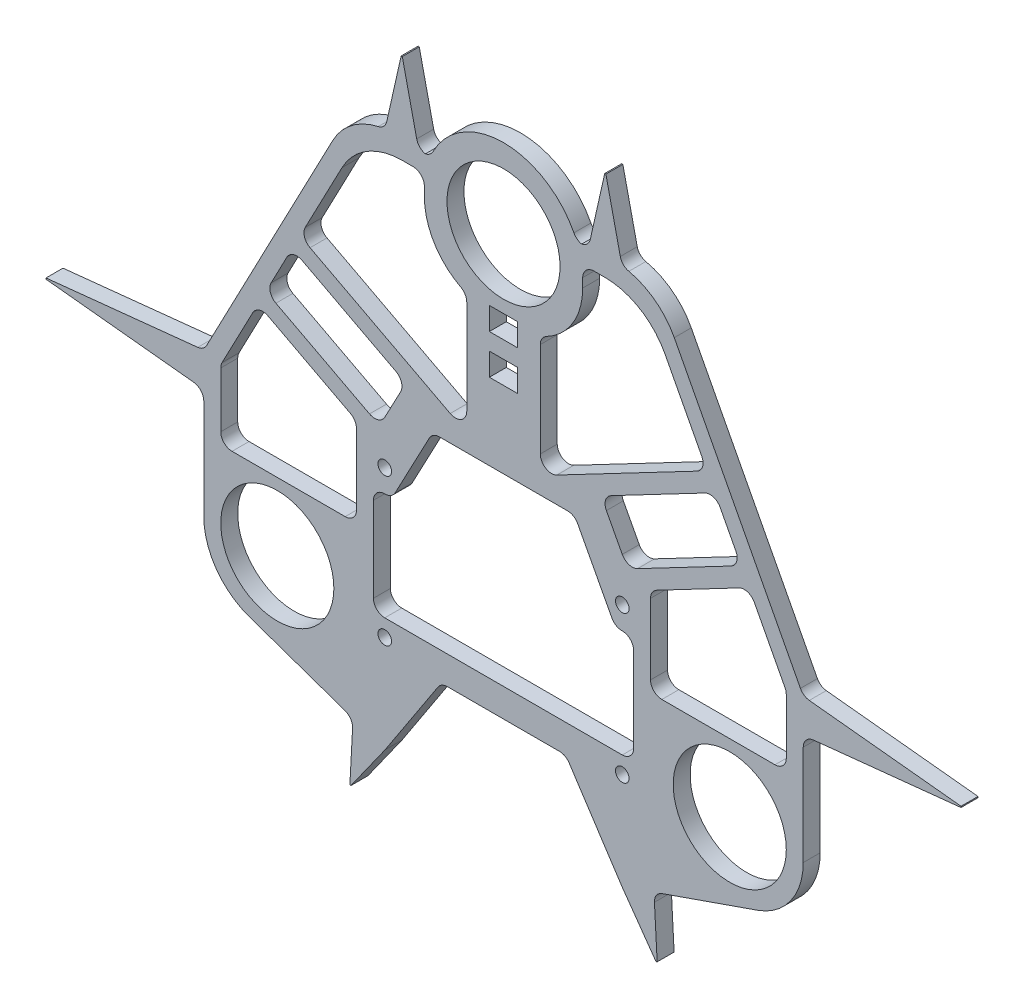
SolidWorks part; units mm, degrees
ref_plane "Plan de face" through (0, 0, 0) normal (0, 0, 1) x (1, 0, 0)
ref_plane "Plan de dessus" through (0, 0, 0) normal (0, 1, 0) x (1, 0, 0)
ref_plane "Plan de droite" through (0, 0, 0) normal (1, 0, 0) x (0, 0, -1)
sketch "Esquisse1" plane through (0, 0, 0) normal (0, 0, 1) x (1, 0, 0)
  line L0 (-40, 0) -> (40, 0) construction
  line L1 (40, 0) -> (0, 69.282) construction
  line L2 (0, 69.282) -> (-40, 0) construction
  line L3 (0, 0) -> (0, 69.282) construction
  line L12 (53, -24) -> (53, 25) construction
  line L13 (-53, 74.6) -> (53, 74.6) construction
  line L14 (-53, 74.6) -> (-53, -24) construction
  line L15 (-53, -24) -> (53, -24) construction
  line L16 (53, 74.6) -> (53, -24) construction
  line L17 (53, 25) -> (27, 74.6) construction
  line L18 (27, 74.6) -> (-27, 74.6) construction
  line L19 (-27, 74.6) -> (-53, 25) construction
  line L20 (-53, 25) -> (-53, -24) construction
  line L21 (40, 25) -> (-40, 25) construction
  line L22 (-40, 4) -> (40, 4) construction
  line L23 (-40, 4) -> (-40, -4) construction
  line L24 (-40, -4) -> (40, -4) construction
  line L25 (40, 4) -> (40, -4) construction
  line L26 (-34, 29) -> (34, 29) construction
  line L27 (-34, 29) -> (-34, 21) construction
  line L28 (-34, 21) -> (34, 21) construction
  line L29 (34, 29) -> (34, 21) construction
  line L30 (-4, 69.282) -> (4, 69.282) construction
  line L31 (-4, 69.282) -> (-4, -4) construction
  line L32 (-4, -4) -> (4, -4) construction
  line L33 (4, 69.282) -> (4, -4) construction
  line L34 (34, 39) -> (34, 11) construction
  line L81 (-27, 74.6) -> (27, 74.6) construction
  line L83 (53, 25) -> (53, -24) construction
  line L84 (53, -24) -> (-53, -24) construction
  line L85 (-53, -24) -> (-53, 25) construction
  line L103 (-53, -9) -> (-10, -24) construction
  line L104 (53, 25) -> (80.9, 22.1)
  line L105 (80.9, 22.1) -> (80.9, 21.9)
  line L106 (80.9, 21.9) -> (53, 19)
  line L107 (53, 19) -> (53, -9)
  line L108 (53, -9) -> (10, -24) construction
  line L109 (10, -24) -> (-10, -24) construction
  line L110 (-53, 19) -> (-53, -9)
  line L111 (-80.9, 21.9) -> (-53, 19)
  line L112 (-53, 25) -> (-80.9, 22.1)
  line L113 (-80.9, 22.1) -> (-80.9, 21.9)
  line L114 (53, 22) -> (80.9, 22) construction
  line L116 (21, 74.6) -> (18.1, 87.5)
  line L117 (18.1, 87.5) -> (17.9, 87.5)
  line L118 (17.9, 87.5) -> (15, 74.6)
  line L119 (15, 74.6) -> (-15, 74.6) construction
  line L120 (15, 74.6) -> (21, 74.6) construction
  line L121 (18, 74.6) -> (18, 87.5) construction
  line L122 (-17.9, 87.5) -> (-15, 74.6)
  line L123 (-18.1, 87.5) -> (-17.9, 87.5)
  line L124 (-21, 74.6) -> (-18.1, 87.5)
  line L126 (-15, 74.6) -> (-12.9506, 74.6)
  line L127 (15, 74.6) -> (12.9506, 74.6)
  line L128 (-53, -9) -> (-20, -20.5116) construction
  line L131 (20, -20.5116) -> (53, -9) construction
  line L132 (-20, -20.5116) -> (20, -20.5116) construction
  line L133 (53, -9) -> (26.6094, -18.206)
  line L134 (26.6094, -18.206) -> (27.1649, -28.6032)
  line L135 (27.1649, -28.6032) -> (26.9761, -28.6691)
  line L136 (26.9761, -28.6691) -> (20.9442, -20.1823)
  line L138 (-53, -9) -> (-26.6094, -18.206)
  line L139 (-26.6094, -18.206) -> (-27.1649, -28.6032)
  line L140 (-27.1649, -28.6032) -> (-26.9761, -28.6691)
  line L141 (-26.9761, -28.6691) -> (-20.9442, -20.1823)
  line L143 (20.9442, -20.1823) -> (26.6094, -18.206) construction
  line L144 (23.7768, -19.1941) -> (27.0705, -28.6361) construction
  line L145 (-40, 0) -> (20, 34.641) construction
  line L146 (40, 0) -> (-20, 34.641) construction
  line L147 (-2.5, 53.094) -> (2.5, 53.094)
  line L148 (-2.5, 57.094) -> (2.5, 57.094)
  line L149 (-2.5, 57.094) -> (-2.5, 53.094)
  line L151 (2.5, 57.094) -> (2.5, 53.094)
  line L196 (-47, 23) -> (-47, 13) construction
  line L197 (-14, 56.094) -> (-7, 56.094) construction
  line L202 (14.0909, -20.5116) -> (-20, -20.5116)
  line L211 (21, 23) -> (-21, 23) construction
  line L227 (-2.5, 50.094) -> (2.5, 50.094)
  line L228 (2.5, 50.094) -> (2.5, 46.094)
  line L229 (2.5, 46.094) -> (-2.5, 46.094)
  line L230 (-2.5, 46.094) -> (-2.5, 50.094)
  line L231 (21, 74.6) -> (27, 74.6)
  line L232 (17.2502, 37.793) -> (37.3765, 48.3431) construction
  line L233 (-11, -5) -> (11, -5)
  line L234 (-11, -5) -> (-20.9442, -20.1823)
  line L235 (11, -5) -> (20.9442, -20.1823)
  line L236 (27, 74.6) -> (53, 25)
  line L237 (21.6982, 29.3986) -> (20.7618, 31.1659) construction
  line L238 (-21, 74.6) -> (-27, 74.6)
  line L239 (40.9789, 39.0491) -> (22.3741, 29.1909) construction
  line L240 (21.9323, 28.9568) -> (17.2502, 37.793)
  line L241 (17.692, 38.0271) -> (35.811, 47.6279) construction
  line L242 (18.4207, 35.584) -> (17.4843, 37.3512) construction
  line L243 (-27, 74.6) -> (-53, 25)
  line L245 (-21.9323, 28.9568) -> (-17.2502, 37.793)
  line L246 (17.2502, 37.793) -> (37.3765, 48.3431)
  line L247 (-21, 74.6) -> (-18.1, 87.5)
  line L248 (-17.9, 87.5) -> (-15, 74.6)
  line L249 (37.3765, 48.3431) -> (42.0192, 39.4862)
  line L250 (42.0192, 39.4862) -> (21.9323, 28.9568)
  line L251 (14, 71.6) -> (25.1854, 71.6)
  line L252 (25.1854, 71.6) -> (35.9837, 51.0002)
  line L253 (35.9837, 51.0002) -> (6.5, 35.545)
  line L254 (6.5, 35.545) -> (6.5, 57.6)
  line L255 (6.5, 57.6) -> (14, 57.6)
  line L256 (14, 57.6) -> (14, 71.6)
  line L257 (43.412, 36.8292) -> (50, 24.2614)
  line L258 (50, 24.2614) -> (50, 12)
  line L259 (50, 12) -> (26, 12)
  line L260 (26, 12) -> (26, 27.7019)
  line L261 (26, 27.7019) -> (43.412, 36.8292)
  line L262 (-23, 19) -> (23, 19) construction
  line L263 (23, 19) -> (23, 0)
  line L264 (23, 0) -> (-23, 0)
  line L265 (-23, 0) -> (-23, 19)
  line L266 (-26, 27.7019) -> (-43.412, 36.8292)
  line L267 (-26, 12) -> (-26, 27.7019)
  line L268 (-50, 12) -> (-26, 12)
  line L269 (-50, 24.2614) -> (-50, 12)
  line L270 (-43.412, 36.8292) -> (-50, 24.2614)
  line L271 (-42.0192, 39.4862) -> (-21.9323, 28.9568)
  line L273 (-37.3765, 48.3431) -> (-42.0192, 39.4862)
  line L274 (-17.2502, 37.793) -> (-37.3765, 48.3431)
  line L275 (-14, 71.6) -> (-25.1854, 71.6)
  line L276 (-14, 57.6) -> (-14, 71.6)
  line L277 (-6.5, 57.6) -> (-14, 57.6)
  line L278 (-6.5, 35.545) -> (-6.5, 57.6)
  line L279 (-35.9837, 51.0002) -> (-6.5, 35.545)
  line L280 (-25.1854, 71.6) -> (-35.9837, 51.0002)
  line L281 (-18.6646, 21) -> (-12.5472, 32.545)
  line L282 (-12.5472, 32.545) -> (12.5472, 32.545)
  line L283 (12.5472, 32.545) -> (18.6646, 21)
  line L284 (18.6646, 21) -> (-18.6646, 21) construction
  line L285 (18.6646, 21) -> (19.7244, 19)
  line L286 (19.7244, 19) -> (23, 19)
  line L287 (-23, 19) -> (-19.7244, 19)
  line L288 (-19.7244, 19) -> (-18.6646, 21)
  circle A0 centre (40, 0) radius 10 construction
  circle A1 centre (-40, 0) radius 10 construction
  circle A2 centre (0, 69.282) radius 10 construction
  circle A11 centre (-21, 23) radius 1.2
  circle A13 centre (21, 23) radius 1.2
  circle A14 centre (-40, 0) radius 10
  circle A15 centre (40, 0) radius 10
  circle A16 centre (0, 69.282) radius 10
  arc A17 (-12.9506, 74.6) -> (12.9506, 74.6) centre (0, 69.282) cw
  circle A39 centre (21, -3) radius 1.2
  circle A40 centre (21, -3) radius 2 construction
  circle A41 centre (-21, -3) radius 1.2
  point P18 (-25.25, -20)
  point P21 (-25.25, 50.5)
  point P24 (25.25, 50.5)
  point P113 (0, -24)
  point P126 (0, 74.6)
  point P146 (0, 23.094)
  point P162 (0, 50.5)
  point P168 (0, 44.4936)
  point P171 (0, 50.5)
  point P196 (0, -5)
  point P198 (0, -12.6457)
  dimension "D5" = 20
  dimension "D36" = 20
  dimension "D7" = 2.4
  dimension "D2" = 80
  dimension "D3" = 50.5
  dimension "D4" = 70.5
  dimension "D9" = 106
  dimension "D10" = 106
  dimension "D11" = 98.6
  dimension "D12" = 24
  dimension "D14" = 54
  dimension "D17" = 8
  dimension "D18" = 8
  dimension "D19" = 8
  dimension "D20" = 8
  dimension "D22" = 25
  dimension "D23" = 34
  dimension "D24" = 90
  dimension "D35" = 49
  dimension "D37" = 10
  dimension "D38" = 15
  dimension "D41" = 3
  dimension "D42" = 3
  dimension "D44" = 6
  dimension "D45" = 12.9
  dimension "D46" = 18
  dimension "D47" = 4
  dimension "D40" = 27.9
  dimension "D48" = 40
  dimension "D49" = 0.2
  dimension "D50" = 6
  dimension "D51" = 4
  dimension "D52" = 10
  dimension "D39" = 5
  dimension "D43" = 5
  dimension "D53" = 4
  dimension "D34" = 30
  dimension "D56" = 10
  dimension "D57" = 37
  dimension "D58" = 47
  dimension "D63" = 33
  dimension "D64" = 14
  dimension "D65" = 7
  dimension "D30" = 23
  dimension "D29" = 42
  dimension "D31" = 3
  dimension "D8" = 180
  dimension "D13" = 46
  dimension "D15" = 46
  dimension "D26" = 12
  dimension "D27" = 3
  dimension "D28" = 5
  dimension "D32" = 4
  dimension "D33" = 14
  dimension "D55" = 14
  dimension "D16" = 3
  dimension "D25" = 3
  dimension "D54" = 3
  dimension "D59" = 54
  dimension "D60" = 3
  dimension "D61" = 3
  dimension "D62" = 3
  dimension "D66" = 3
  dimension "D67" = 3
  dimension "D68" = 37.3292
  dimension "D21" = 2
  dimension "D69" = 22
extrude "Boss.-Extru.1" add sketch "Esquisse1" along normal blind 3 contours A17 L126 L122 L123 L124 L238 L243 L112 L113 L111 L110 L138 L139 L140 L141 L234 L233 L235 L136 L135 L134 L133 L107 L106 L105 L104 L236 L231 L116 L117 L118 L127 A13 A11 L280 L275 L276 L277 L278 L279 L273 L270 L266 region at (66.7441, 21.5688, 0)
fillet "Congé1" radius 2 48 edges at (23, 0, 1.5) (-21, 74.6, 1.5) (-12.9506, 74.6, 1.5) (-15, 74.6, 1.5) (12.9506, 74.6, 1.5) (15, 74.6, 1.5) (21, 74.6, 1.5) (53, 19, 1.5) (11, -5, 1.5) (26.6094, -18.206, 1.5) (26, 12, 1.5) (50, 12, 1.5) (50, 24.2614, 1.5) (53, 25, 1.5) (17.2502, 37.793, 1.5) (21.9323, 28.9568, 1.5) (26, 27.7019, 1.5) (43.412, 36.8292, 1.5) (42.0192, 39.4862, 1.5) (37.3765, 48.3431, 1.5) (35.9837, 51.0002, 1.5) (14, 71.6, 1.5) (-14, 71.6, 1.5) (-6.5, 57.6, 1.5) (6.5, 57.6, 1.5) (6.5, 35.545, 1.5) (12.5472, 32.545, 1.5) (-12.5472, 32.545, 1.5) (-6.5, 35.545, 1.5) (-17.2502, 37.793, 1.5) (-21.9323, 28.9568, 1.5) (-26, 27.7019, 1.5) (-26, 12, 1.5) (-23, 0, 1.5) (-11, -5, 1.5) (-26.6094, -18.206, 1.5) (-50, 12, 1.5) (-53, 19, 1.5) (-53, 25, 1.5) (-50, 24.2614, 1.5) (-43.412, 36.8292, 1.5) (-42.0192, 39.4862, 1.5) (-37.3765, 48.3431, 1.5) (-35.9837, 51.0002, 1.5) (23, 19, 1.5) (19.7244, 19, 1.5) (-19.7244, 19, 1.5) (-23, 19, 1.5)
fillet "Congé2" radius 12 8 edges at (-14, 57.6, 1.5) (14, 57.6, 1.5) (25.1854, 71.6, 1.5) (27, 74.6, 1.5) (-27, 74.6, 1.5) (-25.1854, 71.6, 1.5) (53, -9, 1.5) (-53, -9, 1.5)
equation "\"D16@Esquisse1\"=\"D27@Esquisse1\""
equation "\"D25@Esquisse1\"=\"D27@Esquisse1\""
equation "\"D54@Esquisse1\"=\"D27@Esquisse1\""
equation "\"D60@Esquisse1\"=\"D27@Esquisse1\""
equation "\"D61@Esquisse1\"=\"D27@Esquisse1\""
equation "\"D62@Esquisse1\"=\"D27@Esquisse1\""
equation "\"D66@Esquisse1\"=\"D27@Esquisse1\""
equation "\"D67@Esquisse1\"=\"D27@Esquisse1\""
